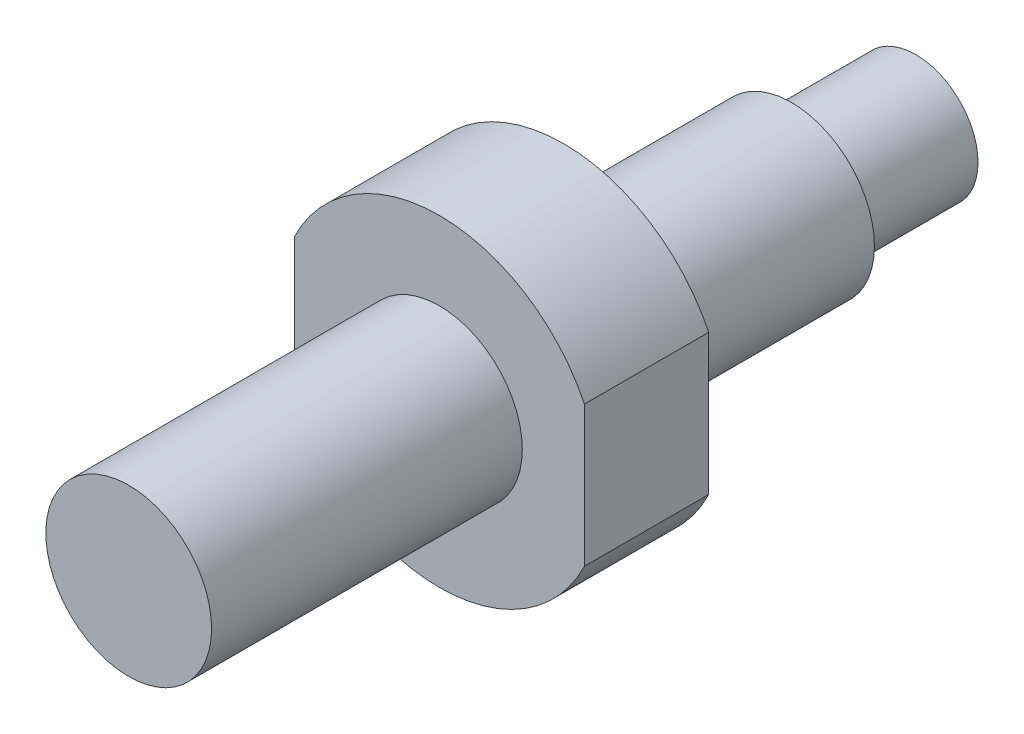
SolidWorks part; units mm, degrees
material "普通碳钢"
ref_plane "前视基准面" through (0, 0, 0) normal (0, 0, 1) x (1, 0, 0)
ref_plane "上视基准面" through (0, 0, 0) normal (0, 1, 0) x (1, 0, 0)
ref_plane "右视基准面" through (0, 0, 0) normal (1, 0, 0) x (0, 0, -1)
sketch "草图2" plane through (0, 0, 0) normal (1, 0, 0) x (0, 0, -1)
  line L0 (0, 0) -> (128.8801, 0) construction
  line L1 (0, 0) -> (0, 4)
  line L2 (0, 4) -> (15, 4)
  line L7 (15, 4) -> (15, 9)
  line L8 (15, 9) -> (21, 9)
  line L9 (21, 9) -> (21, 4)
  line L10 (21, 4) -> (32, 4)
  line L11 (32, 4) -> (32, 0)
  line L12 (0, 0) -> (32, 0)
  dimension "D1" = 15
  dimension "D2" = 4
  dimension "D6" = 6
  dimension "D7" = 4
  dimension "D8" = 9
  dimension "D9" = 11
revolve "旋转1" add sketch "草图2" angle 360 about L0
cosmetic thread "装饰螺纹线1" parameters "D1"=11, "D2"=7
sketch "草图3" plane through (0, 0, -15) normal (0, 0, 1) x (1, 0, 0)
  line L0 (0, 0) -> (0, -7.8258) construction
  line L1 (-7, 8.3859) -> (-15, 8.3859)
  line L2 (7, -8.438) -> (15, -8.438)
  line L3 (7, -8.438) -> (7, 8.3859)
  line L4 (7, 8.3859) -> (15, 8.3859)
  line L5 (15, -8.438) -> (15, 8.3859)
  line L6 (-7, -8.438) -> (-15, -8.438)
  line L7 (-7, -8.438) -> (-7, 8.3859)
  line L8 (-15, -8.438) -> (-15, 8.3859)
  dimension "D1" = 7
  dimension "D2" = 8
extrude "切除-拉伸1" cut sketch "草图3" against normal blind 10
sketch "草图5" plane through (0, 0, -21) normal (0, 0, -1) x (-1, 0, 0)
  circle A0 centre (0, 0) radius 7.7778
extrude "切除-拉伸2" cut sketch "草图5" against normal blind 10 flip side to cut
ref_axis "基准轴1" through (0, 0, -32) along (0, 0, 1)
sketch "草图6" plane through (0, 0, -32) normal (0, 0, -1) x (-1, 0, 0)
  circle A0 centre (0, 0) radius 3
  dimension "D1" = 6
extrude "凸台-拉伸1" add sketch "草图6" along normal blind 6
cosmetic thread "装饰螺纹线2" parameters "D1"=6, "D2"=5
